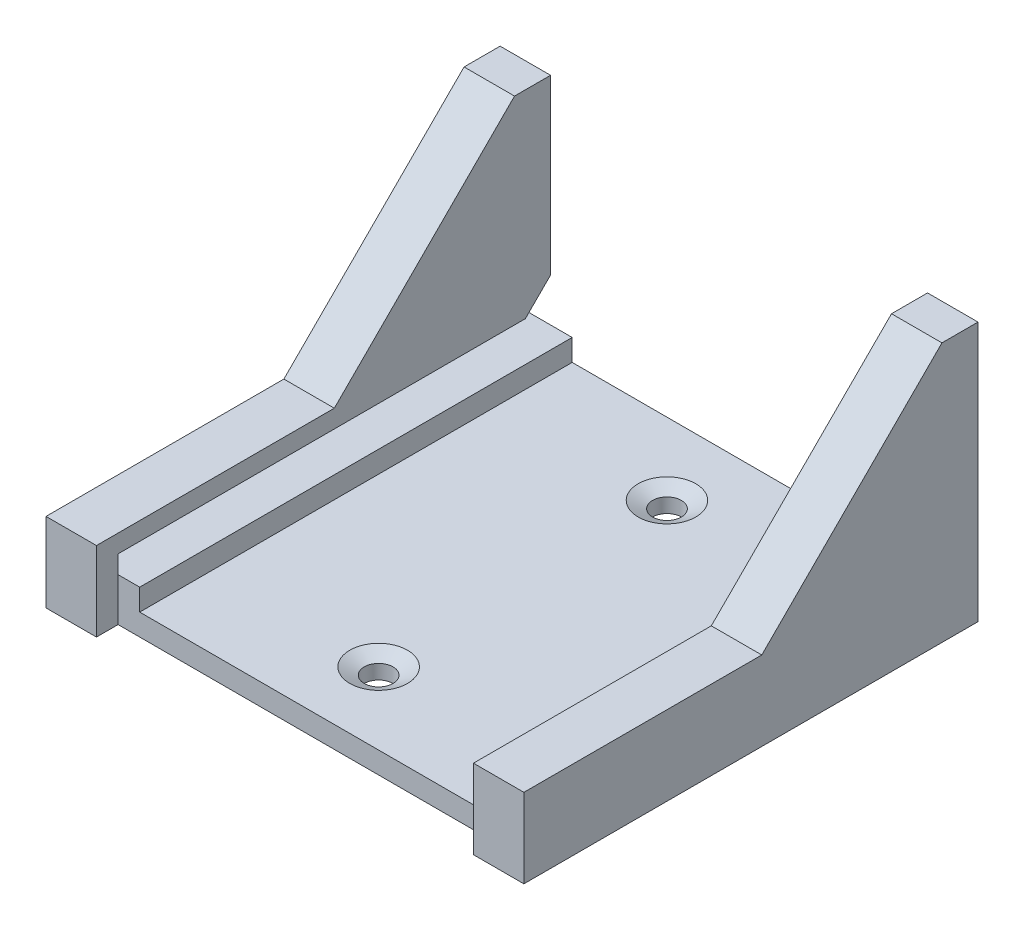
SolidWorks part; units mm, degrees
ref_plane "Спереди" through (0, 0, 0) normal (0, 0, 1) x (1, 0, 0)
ref_plane "Сверху" through (0, 0, 0) normal (0, 1, 0) x (1, 0, 0)
ref_plane "Справа" through (0, 0, 0) normal (1, 0, 0) x (0, 0, -1)
sketch "Эскиз1" plane through (0, 0, 0) normal (0, 0, 1) x (1, 0, 0)
  line L1 (0, 0) -> (66.3, 0)
  line L2 (0, 0) -> (0, 3)
  line L3 (0, 3) -> (66.3, 3)
  line L4 (66.3, 0) -> (66.3, 3)
  dimension "D1" = 66.3
  dimension "D2" = 3
extrude "base" add sketch "Эскиз1" along normal blind 60
sketch "Эскиз2" plane through (0, 0, 0) normal (0, 0, 1) x (1, 0, 0)
  line L0 (66.3, 3) -> (0, 3) construction
  line L1 (0, 3) -> (10, 3)
  line L2 (0, 3) -> (0, 11)
  line L3 (0, 11) -> (7, 11)
  line L4 (59.3, 11) -> (59.3, 8.5)
  line L5 (3, 6) -> (3, 8.5)
  line L6 (3, 8.5) -> (7, 8.5)
  line L7 (33.15, 3) -> (33.15, 0) construction
  line L8 (0, 0) -> (66.3, 0) construction
  line L9 (56.3, 6) -> (56.3, 3)
  line L10 (63.3, 6) -> (56.3, 6)
  line L11 (63.3, 8.5) -> (59.3, 8.5)
  line L12 (63.3, 6) -> (63.3, 8.5)
  line L13 (66.3, 11) -> (59.3, 11)
  line L14 (66.3, 3) -> (66.3, 11)
  line L15 (3, 6) -> (10, 6)
  line L16 (10, 6) -> (10, 3)
  line L17 (7, 11) -> (7, 8.5)
  line L18 (66.3, 3) -> (56.3, 3)
  dimension "D1" = 7
  dimension "D2" = 8
  dimension "D3" = 2.5
  dimension "D4" = 10
  dimension "D5" = 3
  dimension "D6" = 3
extrude "rails" add sketch "Эскиз2" along normal up to surface (60 mm away) up to face at (33.15, 1.5, 60)
sketch "Эскиз3" plane through (0, 3, 0) normal (0, 1, 0) x (1, 0, 0)
  line L0 (33.15, 0) -> (33.15, -60) construction
  line L1 (56.3, 0) -> (10, 0) construction
  line L2 (56.3, -60) -> (10, -60) construction
  circle A0 centre (33.15, -10) radius 2
  circle A1 centre (33.15, -50) radius 2
  dimension "D3" = 4
  dimension "D1" = 10
  dimension "D2" = 10
extrude "holes" cut sketch "Эскиз3" against normal through all
chamfer "Фаска1" distance 2 distance2 1 2 edges at (33.15, 3, 12) (33.15, 3, 52) first distance on face at (33.15, 3, 52)
sketch "Эскиз4" plane through (0, 0, 60) normal (0, 0, 1) x (1, 0, 0)
  line L0 (7, 11) -> (7, 8.5) construction
  line L1 (0, 11) -> (7, 11)
  line L2 (0, 11) -> (0, 0)
  line L3 (0, 0) -> (7, 0)
  line L4 (7, 11) -> (7, 0)
  line L5 (0, 0) -> (66.3, 0) construction
  line L6 (66.3, 11) -> (59.3, 11)
  line L7 (66.3, 11) -> (66.3, 0)
  line L8 (66.3, 0) -> (59.3, 0)
  line L9 (59.3, 11) -> (59.3, 0)
  line L10 (59.3, 8.5) -> (59.3, 11) construction
extrude "floor" add sketch "Эскиз4" along normal blind 3
sketch "Эскиз5" plane through (0, 11, 0) normal (0, 1, 0) x (1, 0, 0)
  line L1 (0, 0) -> (7, 0)
  line L2 (0, 0) -> (0, -5)
  line L3 (0, -5) -> (7, -5)
  line L4 (7, 0) -> (7, -5)
  line L5 (33.15, 0) -> (33.15, -60) construction
  line L6 (56.3, 0) -> (10, 0) construction
  line L8 (59.3, 0) -> (59.3, -5)
  line L9 (66.3, -5) -> (59.3, -5)
  line L10 (66.3, 0) -> (66.3, -5)
  line L11 (66.3, 0) -> (59.3, 0)
  line L12 (7, -63) -> (7, 0) construction
  line L13 (56.3, -60) -> (10, -60) construction
  dimension "D1" = 5
extrude "Вытянуть1" add sketch "Эскиз5" along normal blind 25
chamfer "Фаска2" distance 25 angle 45 2 edges at (3.5, 11, 5) (62.8, 11, 5)
chamfer "Фаска3" distance 3.5 angle 45 2 edges at (5, 8.5, 0) (61.3, 8.5, 0)
